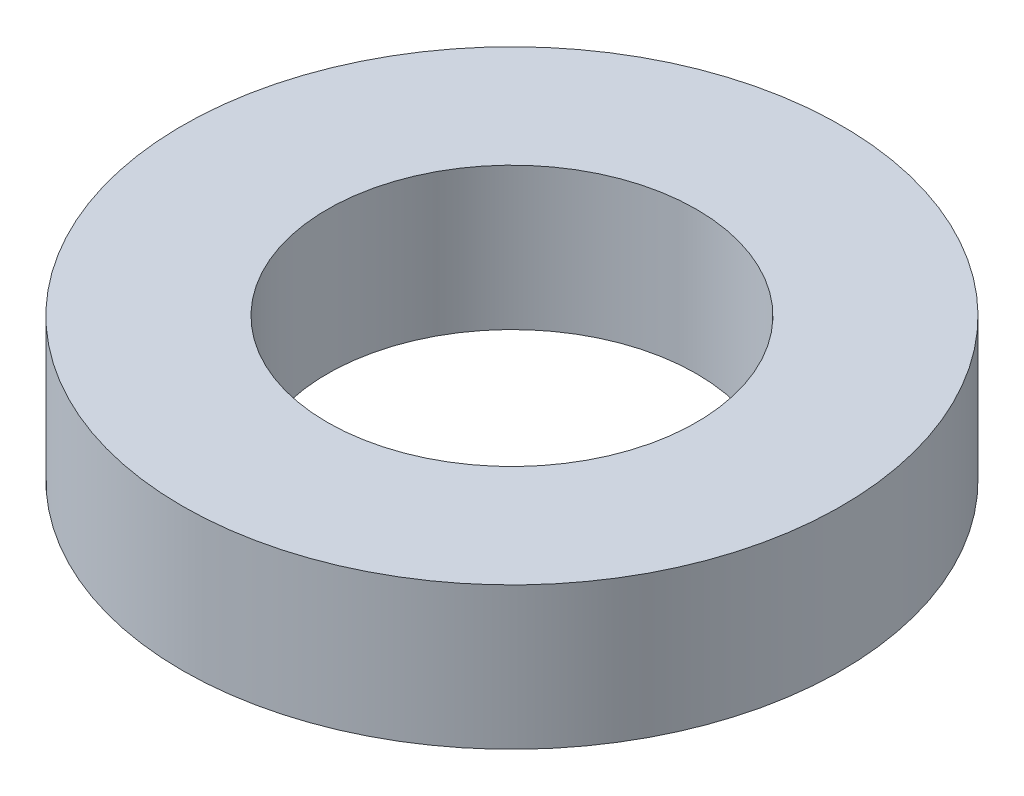
SolidWorks part; units mm, degrees
ref_plane "Front Plane" through (0, 0, 0) normal (0, 0, 1) x (1, 0, 0)
ref_plane "Top Plane" through (0, 0, 0) normal (0, 1, 0) x (1, 0, 0)
ref_plane "Right Plane" through (0, 0, 0) normal (1, 0, 0) x (0, 0, -1)
sketch "Sketch1" plane through (0, 0, 0) normal (0, 1, 0) x (1, 0, 0)
  circle A0 centre (0, 0) radius 62.5
  dimension "FLANGE_OD" = 125
extrude "Boss-Extrude1" add sketch "Sketch1" along normal blind 27
sketch "Sketch2" plane through (0, 0, 0) normal (0, 1, 0) x (1, 0, 0)
  circle A0 centre (0, 0) radius 35
  dimension "BORE_D" = 70
extrude "Cut-Extrude1" cut sketch "Sketch2" along normal through all
sketch "Sketch3" plane through (0, 27, 0) normal (0, 1, 0) x (1, 0, 0)
  circle A0 centre (0, 0) radius 25.6854 construction
  circle A1 centre (-25.6854, 0) radius 3.2879
  dimension "BOLT_D" = 6.5759
  dimension "BOLT_PCD" = 51.3709
extrude "Cut-Extrude2" cut sketch "Sketch3" against normal blind 20.3823 rebuild error yes
pattern_circular "CirPattern1" count 5 over 360 rebuild error yes
